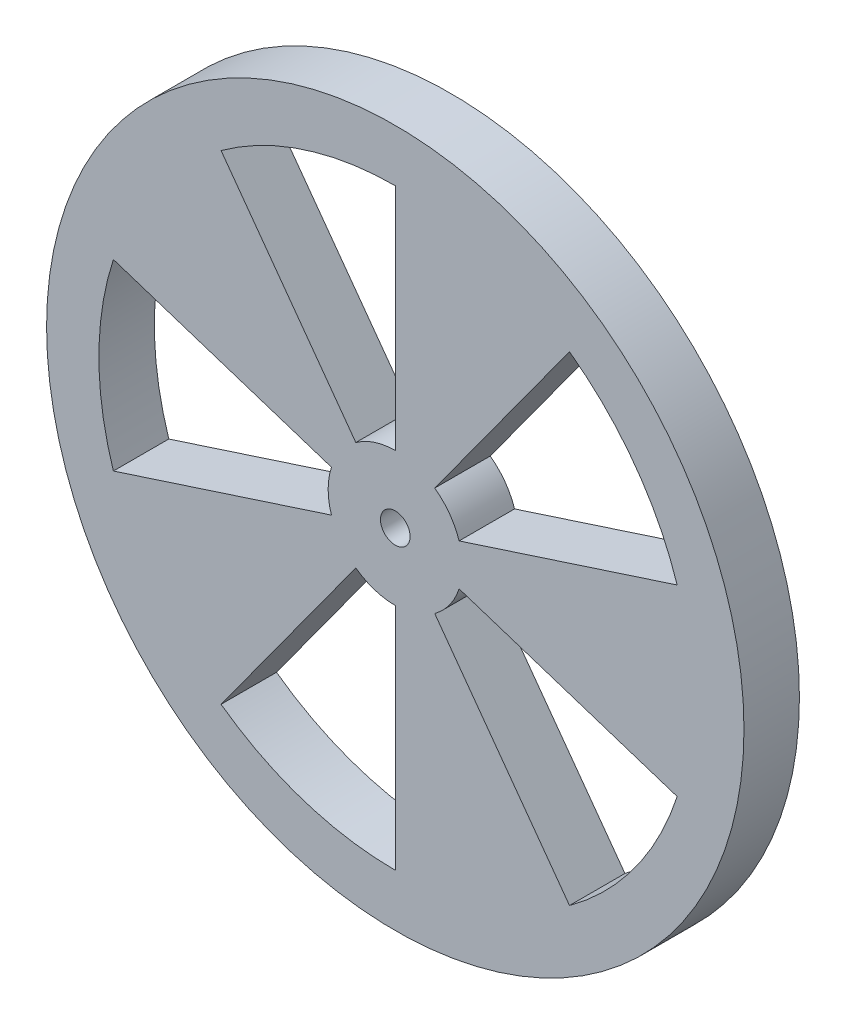
SolidWorks part; units mm, degrees
ref_plane "Front Plane" through (0, 0, 0) normal (0, 0, 1) x (1, 0, 0)
ref_plane "Top Plane" through (0, 0, 0) normal (0, 1, 0) x (1, 0, 0)
ref_plane "Right Plane" through (0, 0, 0) normal (1, 0, 0) x (0, 0, -1)
sketch "Sketch1" plane through (0, 0, 0) normal (0, 0, 1) x (1, 0, 0)
  circle A0 centre (0, 0) radius 20
  circle A1 centre (0, 0) radius 0.85
  dimension "D1" = 40
extrude "Boss-Extrude1" add sketch "Sketch1" along normal blind 3.18
sketch "Sketch2" plane through (0, 0, 3.18) normal (0, 0, 1) x (1, 0, 0)
  line L0 (0, 3.85) -> (0, 17)
  line L1 (2.263, 3.1147) -> (9.9923, 13.7533)
  line L2 (3.6616, 1.1897) -> (16.168, 5.2533)
  line L3 (3.6616, -1.1897) -> (16.168, -5.2533)
  line L4 (2.263, -3.1147) -> (9.9923, -13.7533)
  line L5 (0, -3.85) -> (0, -17)
  line L6 (-2.263, -3.1147) -> (-9.9923, -13.7533)
  line L7 (-3.6616, -1.1897) -> (-16.168, -5.2533)
  line L8 (-3.6616, 1.1897) -> (-16.168, 5.2533)
  line L9 (-2.263, 3.1147) -> (-9.9923, 13.7533)
  circle A0 centre (0, 0) radius 3.85
  circle A1 centre (0, 0) radius 17
  circle A2 centre (0, 0) radius 20 construction
  circle A3 centre (0, 0) radius 0.85 construction
  circle A4 centre (0, 0) radius 17
  circle A5 centre (0, 0) radius 17
  circle A6 centre (0, 0) radius 17
  circle A7 centre (0, 0) radius 17
  circle A8 centre (0, 0) radius 17
  circle A9 centre (0, 0) radius 17
  circle A10 centre (0, 0) radius 17
  circle A11 centre (0, 0) radius 17
  circle A12 centre (0, 0) radius 17
  circle A13 centre (0, 0) radius 17
  circle A14 centre (0, 0) radius 17
  circle A15 centre (0, 0) radius 17
  circle A16 centre (0, 0) radius 17
  circle A17 centre (0, 0) radius 17
  circle A18 centre (0, 0) radius 17
  circle A19 centre (0, 0) radius 17
  circle A20 centre (0, 0) radius 17
  circle A21 centre (0, 0) radius 17
  circle A22 centre (0, 0) radius 17
  circle A23 centre (0, 0) radius 17
  circle A24 centre (0, 0) radius 17
  circle A25 centre (0, 0) radius 17
  circle A26 centre (0, 0) radius 17
  circle A27 centre (0, 0) radius 17
  circle A28 centre (0, 0) radius 17
  circle A29 centre (0, 0) radius 17
  circle A30 centre (0, 0) radius 17
  circle A31 centre (0, 0) radius 17
  circle A32 centre (0, 0) radius 17
  point P34 (0, 0)
  point P42 (0, 0)
  point P101 (0, 0)
  dimension "D1" = 3
  dimension "D2" = 3
  dimension "D3" = 10
extrude "Cut-Extrude1" cut sketch "Sketch2" against normal through all contours L0 A1 L9 A0 | L8 A1 L7 A0 | L6 A1 L5 A0 | L4 A1 L3 A0 | L2 A1 L1 A0 region at (-3.5889, 11.0456, 3.18) region at (9.3959, 6.8265, 3.18) region at (-11.614, 0, 3.18) region at (9.3959, -6.8265, 3.18) region at (-3.5889, -11.0456, 3.18)
